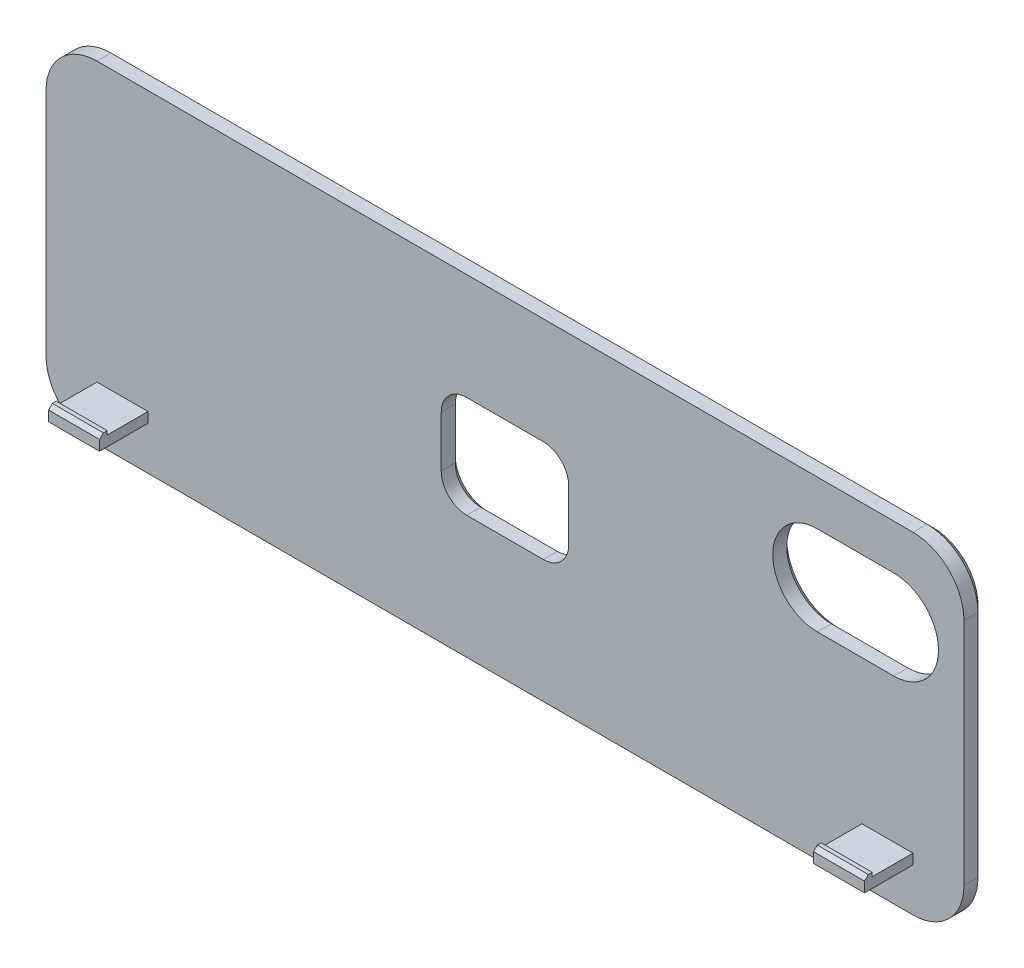
SolidWorks part; units mm, degrees
ref_plane "Front Plane" through (0, 0, 0) normal (0, 0, 1) x (1, 0, 0)
ref_plane "Top Plane" through (0, 0, 0) normal (0, 1, 0) x (1, 0, 0)
ref_plane "Right Plane" through (0, 0, 0) normal (1, 0, 0) x (0, 0, -1)
sketch "Sketch1" plane through (0, 0, 0) normal (0, 0, 1) x (1, 0, 0)
  line L0 (-32, 8.6) -> (32, 8.6)
  line L1 (36, 12.6) -> (36, 30.6)
  line L2 (32, 34.6) -> (-32, 34.6)
  line L3 (-36, 30.6) -> (-36, 12.6)
  arc A0 (-36, 12.6) -> (-32, 8.6) centre (-32, 12.6) ccw
  arc A1 (32, 8.6) -> (36, 12.6) centre (32, 12.6) ccw
  arc A2 (36, 30.6) -> (32, 34.6) centre (32, 30.6) ccw
  arc A3 (-32, 34.6) -> (-36, 30.6) centre (-32, 30.6) ccw
extrude "Boss-Extrude1" add sketch "Sketch1" along normal blind 1.6 from offset 80 offset against normal yes
chamfer "Chamfer1" distance 0.5 angle 45 8 edges at (0, 8.6, -80) (34.8284, 9.7716, -80) (-34.8284, 9.7716, -80) (36, 21.6, -80) (-36, 21.6, -80) (34.8284, 33.4284, -80) (-34.8284, 33.4284, -80) (0, 34.6, -80)
sketch "Sketch2" plane through (0, 0, 0) normal (0, 0, 1) x (1, 0, 0)
  line L0 (-3, 18.25) -> (3, 18.25)
  line L1 (5, 20.25) -> (5, 24.25)
  line L2 (3, 26.25) -> (-3, 26.25)
  line L3 (-5, 24.25) -> (-5, 20.25)
  arc A0 (-5, 20.25) -> (-3, 18.25) centre (-3, 20.25) ccw
  arc A1 (3, 18.25) -> (5, 20.25) centre (3, 20.25) ccw
  arc A2 (5, 24.25) -> (3, 26.25) centre (3, 24.25) ccw
  arc A3 (-3, 26.25) -> (-5, 24.25) centre (-3, 24.25) ccw
extrude "Boss-Extrude2" add sketch "Sketch2" along normal blind 3 from offset 81 separate body offset against normal yes
combine bodies "Combine1" operation type subtract main body 101 bodies to subtract 102
chamfer "Chamfer2" distance 0.5 angle 45 8 edges at (0, 18.25, -80) (-4.4142, 18.8358, -80) (4.4142, 18.8358, -80) (-5, 22.25, -80) (5, 22.25, -80) (-4.4142, 25.6642, -80) (4.4142, 25.6642, -80) (0, 26.25, -80)
sketch "Sketch3" plane through (0, 0, 0) normal (0, 0, 1) x (1, 0, 0)
  line L0 (24.5, 24.08) -> (30.5, 24.08)
  line L1 (30.5, 31.08) -> (24.5, 31.08)
  arc A0 (21, 27.58) -> (24.5, 24.08) centre (24.5, 27.58) ccw
  arc A1 (30.5, 24.08) -> (34, 27.58) centre (30.5, 27.58) ccw
  arc A2 (34, 27.58) -> (30.5, 31.08) centre (30.5, 27.58) ccw
  arc A3 (24.5, 31.08) -> (21, 27.58) centre (24.5, 27.58) ccw
extrude "Boss-Extrude3" add sketch "Sketch3" along normal blind 3 from offset 81 separate body offset against normal yes
combine bodies "Combine2" operation type subtract main body 103 bodies to subtract 104
chamfer "Chamfer3" distance 0.5 angle 45 1 edges at (27.5, 31.08, -80)
sketch "Sketch4" plane through (0, 0, 0) normal (0, 0, 1) x (1, 0, 0)
  line L1 (-1.5, 8.5) -> (1.5, 8.5)
  line L2 (-1.5, 8.5) -> (-1.5, 9.4)
  line L3 (-1.5, 9.4) -> (1.5, 9.4)
  line L4 (1.5, 8.5) -> (1.5, 9.4)
extrude "Boss-Extrude4" add sketch "Sketch4" along normal blind 0.9 from offset 80.1 separate body offset against normal yes
combine bodies "Combine3" operation type subtract main body 105 bodies to subtract 106
sketch "Sketch5" plane through (0, 0, 0) normal (1, 0, 0) x (0, 0, -1)
  line L0 (78.41, 12) -> (74.6, 12)
  line L1 (74.6, 12) -> (74.6, 12.8)
  line L2 (74.6, 12.8) -> (74.9, 13.1)
  line L3 (74.9, 13.1) -> (75.2, 13.1)
  line L4 (75.2, 13.1) -> (75.2, 12.8)
  line L5 (75.2, 12.8) -> (78.41, 12.8)
  line L6 (78.41, 12.8) -> (78.41, 12)
extrude "Boss-Extrude5" add sketch "Sketch5" along normal blind 4 from offset 32 offset against normal yes
sketch "Sketch6" plane through (0, 0, 0) normal (1, 0, 0) x (0, 0, -1)
  line L0 (78.41, 12) -> (74.6, 12)
  line L1 (74.6, 12) -> (74.6, 12.8)
  line L2 (74.6, 12.8) -> (74.9, 13.1)
  line L3 (74.9, 13.1) -> (75.2, 13.1)
  line L4 (75.2, 13.1) -> (75.2, 12.8)
  line L5 (75.2, 12.8) -> (78.41, 12.8)
  line L6 (78.41, 12.8) -> (78.41, 12)
extrude "Boss-Extrude6" add sketch "Sketch6" along normal blind 4 from offset 28
